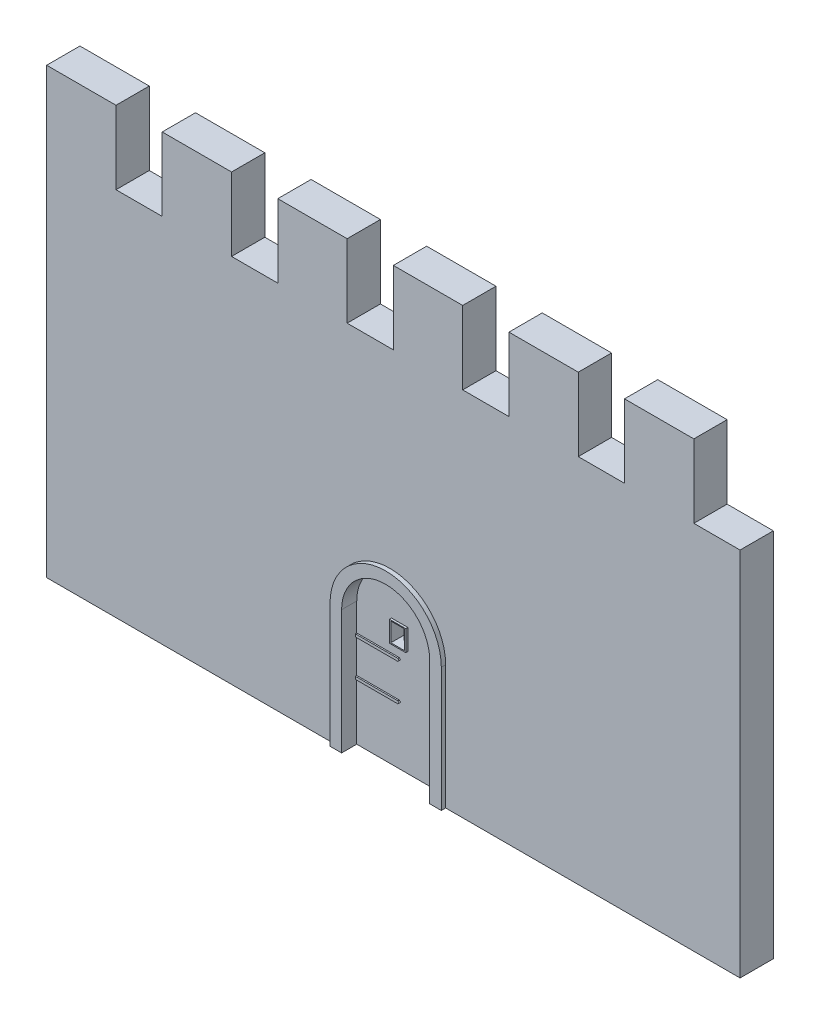
SolidWorks part; units mm, degrees
ref_plane "Front Plane" through (0, 0, 0) normal (0, 0, 1) x (1, 0, 0)
ref_plane "Top Plane" through (0, 0, 0) normal (0, 1, 0) x (1, 0, 0)
ref_plane "Right Plane" through (0, 0, 0) normal (1, 0, 0) x (0, 0, -1)
sketch "Sketch1" plane through (0, 0, 0) normal (0, 0, 1) x (1, 0, 0)
  line L1 (0, 0) -> (38100, 0)
  line L2 (0, 0) -> (0, 24384)
  line L3 (0, 24384) -> (38100, 24384)
  line L4 (38100, 0) -> (38100, 24384)
  dimension "D1" = 38100
  dimension "D2" = 24384
extrude "Boss-Extrude1" add sketch "Sketch1" along normal blind 1828.8
sketch "Sketch2" plane through (0, 0, 1828.8) normal (0, 0, 1) x (1, 0, 0)
  line L0 (0, 24384) -> (0, 20364.7506)
  line L1 (0, 24384) -> (0, 0) construction
  line L2 (0, 20364.7506) -> (3810, 20364.7506)
  line L3 (3810, 20364.7506) -> (3810, 24384)
  line L4 (38100, 24384) -> (0, 24384) construction
  line L5 (3810, 24384) -> (0, 24384)
  line L6 (6350, 24384) -> (6350, 20364.7506)
  line L7 (6350, 20364.7506) -> (10160, 20364.7506)
  line L8 (10160, 20364.7506) -> (10160, 24384)
  line L9 (10160, 24384) -> (6350, 24384)
  line L10 (11430, 24384) -> (12700, 24384)
  line L11 (16510, 24384) -> (19050, 24384)
  line L12 (16510, 24384) -> (19050, 24384)
  line L13 (6350, 24384) -> (11430, 24384)
  line L14 (19050, 24384) -> (19050, 20364.7506)
  line L15 (19050, 20364.7506) -> (22860, 20364.7506)
  line L16 (22860, 20364.7506) -> (22860, 24384)
  line L17 (22860, 24384) -> (19050, 24384)
  line L18 (25400, 24384) -> (25400, 20364.7506)
  line L19 (25400, 20364.7506) -> (29210, 20364.7506)
  line L20 (29210, 20364.7506) -> (29210, 24384)
  line L21 (29210, 24384) -> (25400, 24384)
  line L22 (31750, 24384) -> (31750, 20364.7506)
  line L23 (31750, 24384) -> (35560, 24384)
  line L24 (38100, 20364.7506) -> (38100, 24384)
  line L25 (3810, 20364.7506) -> (6350, 20364.7506)
  line L26 (3810, 24384) -> (6350, 24384)
  line L27 (10160, 24384) -> (11430, 24384)
  line L28 (11430, 24384) -> (10160, 24384)
  line L29 (16510, 24384) -> (19050, 24384)
  line L30 (22860, 24384) -> (25400, 24384)
  line L31 (10160, 24384) -> (12700, 24384)
  line L32 (16510, 24384) -> (19050, 24384)
  line L33 (12700, 24384) -> (16510, 24384)
  line L34 (12700, 24384) -> (12700, 20364.7506)
  line L35 (12700, 20364.7506) -> (16510, 20364.7506)
  line L36 (16510, 24384) -> (16510, 20364.7506)
  line L37 (6350, 24384) -> (12700, 24384)
  line L38 (22860, 24384) -> (25400, 24384)
  line L39 (12700, 20364.7506) -> (10160, 20364.7506)
  line L40 (22860, 24384) -> (25400, 24384)
  line L41 (29210, 24384) -> (31750, 24384)
  line L42 (35560, 20364.7506) -> (35560, 24384)
  line L43 (31750, 20364.7506) -> (35560, 20364.7506)
  line L44 (16510, 20364.7506) -> (19050, 20364.7506)
  line L45 (19050, 24384) -> (16510, 24384)
  line L46 (22860, 24384) -> (25400, 24384)
  line L47 (25400, 20364.7506) -> (22860, 20364.7506)
  line L48 (29210, 20364.7506) -> (31750, 20364.7506)
  line L49 (31750, 24384) -> (29210, 24384)
  line L50 (35560, 24384) -> (38100, 24384)
  line L51 (38100, 20364.7506) -> (35560, 20364.7506)
  line L52 (38100, 20364.7506) -> (38100, 24384)
  line M3 (38100, 0) -> (38100, 24384)
  line M4 (38100, 24384) -> (0, 24384)
  dimension "D1" = 2540
  dimension "D2" = 2540
  dimension "D3" = 2540
  dimension "D5" = 3810
extrude "Cut-Extrude2" cut sketch "Sketch2" against normal blind 1828.8 contours L3 L25 L6 M4 | L39 L34 L8 M4 | L36 L44 L14 M4 | L47 L18 L16 M4 | L20 L48 L22 M4 | L51 L42 M3 M4 region at (5080, 22374.3753, 1828.8) region at (11430, 22374.3753, 1828.8) region at (17780, 22374.3753, 1828.8) region at (24130, 22374.3753, 1828.8) region at (30480, 22374.3753, 1828.8) region at (36830, 22374.3753, 1828.8)
sketch "Sketch3" plane through (0, 0, 0) normal (0, 0, -1) x (-1, 0, 0)
  line L0 (0, 0) -> (-38100, 0) construction
  line L1 (-16444.9502, 0) -> (-21288.1413, 0)
  line L2 (-16444.9502, 0) -> (-16444.9502, 6816.7917)
  line L4 (-21288.1413, 0) -> (-21288.1413, 6816.7917)
  arc A0 (-16444.9502, 6816.7917) -> (-21288.1413, 6816.7917) centre (-18866.5458, 6816.7917) ccw
  dimension "D1" = 6816.7917
extrude "Cut-Extrude7" cut sketch "Sketch3" against normal blind 283.464
sketch "Sketch5" plane through (0, 0, 283.464) normal (0, 0, -1) x (-1, 0, 0)
  line L1 (-19182.4488, 6914.3812) -> (-18434.056, 6914.3812)
  line L2 (-19182.4488, 6914.3812) -> (-19182.4488, 5880.1455)
  line L3 (-19182.4488, 5880.1455) -> (-18434.056, 5880.1455)
  line L4 (-18434.056, 6914.3812) -> (-18434.056, 5880.1455)
  line L5 (-21288.1413, 0) -> (-16444.9502, 0)
  line L6 (-21288.1413, 0) -> (-21288.1413, 6816.7917)
sketch "Sketch6" plane through (0, 0, 1828.8) normal (0, 0, 1) x (1, 0, 0)
  line L1 (16444.9502, 0) -> (21288.1413, 0)
  line L2 (16444.9502, 0) -> (16444.9502, 6816.7917)
  line L4 (21288.1413, 0) -> (21288.1413, 6816.7917)
  arc A0 (16444.9502, 6816.7917) -> (18866.5458, 9238.3872) centre (18866.5458, 6816.7917) cw
  arc A1 (21288.1413, 6816.7917) -> (16444.9502, 6816.7917) centre (18866.5458, 6816.7917) ccw construction
  arc A2 (18866.5458, 9238.3872) -> (21288.1413, 6816.7917) centre (18866.5458, 6816.7917) cw
extrude "Cut-Extrude9" cut sketch "Sketch6" against normal blind 593.09
extrude "Cut-Extrude10" cut sketch "Sketch5" against normal blind 2197.608 contours L4 L1 L2 L3 region at (18808.2524, 6397.2633, 283.464)
sketch "Sketch8" plane through (0, 0, 283.464) normal (0, 0, -1) x (-1, 0, 0)
  line L1 (-19182.4488, 5880.1455) -> (-18434.056, 5880.1455)
  line L2 (-19182.4488, 5880.1455) -> (-19182.4488, 6914.3812)
  line L3 (-19182.4488, 6914.3812) -> (-18434.056, 6914.3812)
  line L4 (-18434.056, 5880.1455) -> (-18434.056, 6914.3812)
  line L5 (-19258.6488, 5817.7664) -> (-18357.856, 5817.7664)
  line L6 (-19258.6488, 5817.7664) -> (-19258.6488, 6960.7664)
  line L7 (-19258.6488, 6960.7664) -> (-18357.856, 6960.7664)
  line L8 (-18357.856, 5817.7664) -> (-18357.856, 6960.7664)
  dimension "D1" = 76.2
  dimension "D2" = 76.2
  dimension "D3" = 1143
extrude "Boss-Extrude2" add sketch "Sketch8" along normal blind 127 and the other way blind 1066.8
sketch "Sketch9" plane through (0, 5880.1455, 0) normal (0, 1, 0) x (1, 0, 0)
  line L0 (19182.4488, -1350.264) -> (19182.4488, -156.464) construction
  line L1 (18434.056, -1350.264) -> (18434.056, -156.464) construction
  line L2 (19182.4488, -1350.264) -> (18434.056, -1350.264) construction
  circle A0 centre (18852.2488, -842.264) radius 25.4
  circle A1 centre (19030.0488, -842.2641) radius 25.4
  circle A2 centre (18674.4488, -842.264) radius 25.4
  dimension "D1" = 177.8
  dimension "D2" = 177.8
  dimension "D3" = 152.4
  dimension "D4" = 240.3928
  dimension "D5" = 508
extrude "Boss-Extrude3" add sketch "Sketch9" along normal blind 1070.61
sketch "Sketch10" plane through (0, 0, 1235.71) normal (0, 0, 1) x (1, 0, 0)
  line L0 (16444.9502, 5292.1672) -> (18780.7632, 5292.1672)
  line L1 (16444.9502, 6816.7917) -> (16444.9502, 0) construction
  line L2 (18780.7632, 5292.1672) -> (18853.6355, 5219.2949)
  line L3 (18853.6355, 5219.2949) -> (18780.7632, 5146.4225)
  line L4 (18780.7632, 5146.4225) -> (16444.9502, 5146.4225)
  line L5 (16444.9502, 5146.4225) -> (16444.9502, 5292.1672)
  line L6 (16444.9502, 3271.8048) -> (18780.7632, 3271.8048)
  line L7 (18780.7632, 3271.8048) -> (18853.6355, 3198.9325)
  line L8 (18853.6355, 3198.9325) -> (18780.7632, 3126.0602)
  line L9 (18780.7632, 3126.0602) -> (16444.9502, 3126.0602)
  line L10 (16444.9502, 3126.0602) -> (16444.9502, 3271.8048)
extrude "Boss-Extrude4" add sketch "Sketch10" along normal blind 76.2 and the other way blind 1016
sketch "Sketch11" plane through (0, 0, 1828.8) normal (0, 0, 1) x (1, 0, 0)
  line L0 (0, 0) -> (16444.9502, 0) construction
  line L1 (16444.9502, 0) -> (21288.1413, 0)
  line L2 (16444.9502, 0) -> (16444.9502, 6816.7917)
  line L3 (15809.9502, 0) -> (21923.1413, 0)
  line L4 (21288.1413, 0) -> (21288.1413, 6816.7917)
  line L5 (15809.9502, 0) -> (15809.9502, 6816.7917)
  line L7 (21923.1413, 0) -> (21923.1413, 6816.7917)
  arc A0 (16444.9502, 6816.7917) -> (21288.1413, 6816.7917) centre (18866.5458, 6816.7917) cw
  arc A1 (15809.9502, 6816.7917) -> (21923.1413, 6816.7917) centre (18866.5458, 6816.7917) cw
  line M1 (0, 0) -> (16444.9502, 0)
  line M2 (16444.9502, 0) -> (16444.9502, 6816.7917)
  arc M3 (16444.9502, 6816.7917) -> (21288.1413, 6816.7917) centre (18866.5458, 6816.7917) cw
  line M4 (21288.1413, 6816.7917) -> (21288.1413, 0)
  line M5 (21288.1413, 0) -> (38100, 0)
  dimension "D1" = 635
  dimension "D2" = 635
extrude "Boss-Extrude5" add sketch "Sketch11" along normal blind 238.76 and the other way blind 2032 contours A1 L5 L7 M1 M2 M3 M4 M5 region at (16127.4502, 116.127, 1828.8)
